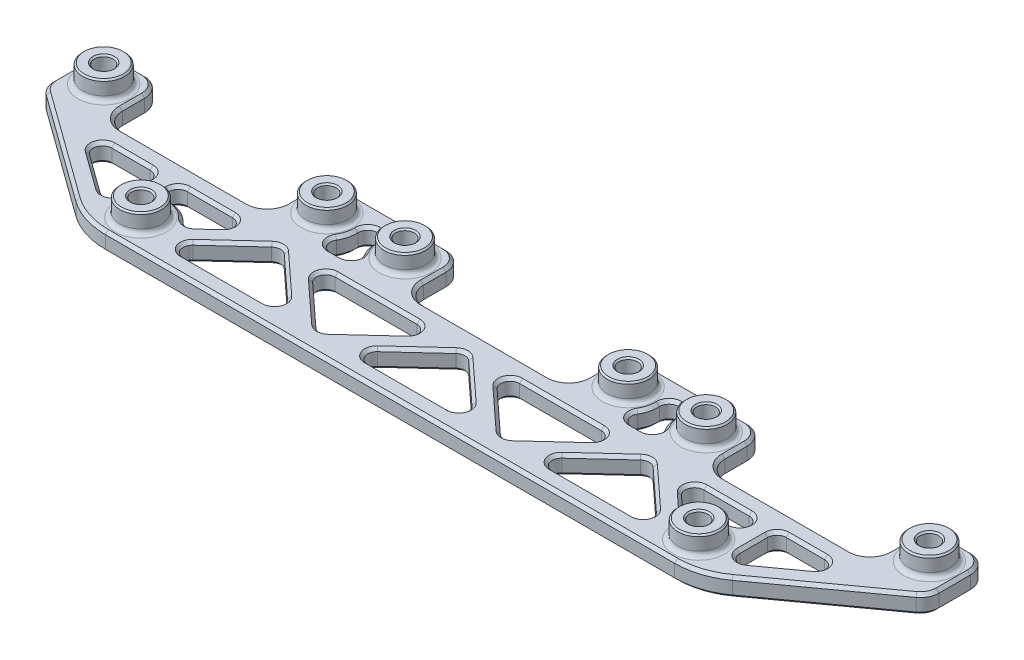
SolidWorks part; units mm, degrees
ref_plane "Front" through (0, 0, 0) normal (0, 0, 1) x (1, 0, 0)
ref_plane "Top" through (0, 0, 0) normal (0, 1, 0) x (1, 0, 0)
ref_plane "Right" through (0, 0, 0) normal (1, 0, 0) x (0, 0, -1)
sketch "Sketch2" plane through (0, 0, 0) normal (0, 1, 0) x (1, 0, 0)
  line L0 (-69.215, 13.335) -> (-68.58, 13.335) construction
  line L5 (-75.565, 3.175) -> (-65.405, 3.175) construction
  line L6 (-75.565, 3.175) -> (-75.565, 13.335) construction
  line L7 (-75.565, 13.335) -> (-65.405, 13.335) construction
  line L8 (-65.405, 3.175) -> (-65.405, 13.335) construction
  line L9 (-75.565, 3.175) -> (-65.405, 13.335) construction
  line L10 (-75.565, 13.335) -> (-65.405, 3.175) construction
  line L11 (-65.405, 10.16) -> (-65.405, 9.525) construction
  line L12 (-34.29, 13.335) -> (-33.655, 13.335) construction
  line L13 (-27.305, 3.175) -> (-37.465, 3.175) construction
  line L14 (-27.305, 3.175) -> (-27.305, 13.335) construction
  line L15 (-27.305, 13.335) -> (-37.465, 13.335) construction
  line L16 (-37.465, 3.175) -> (-37.465, 13.335) construction
  line L17 (-27.305, 3.175) -> (-37.465, 13.335) construction
  line L18 (-27.305, 13.335) -> (-37.465, 3.175) construction
  line L19 (-37.465, 9.525) -> (-37.465, 10.16) construction
  line L20 (-17.78, 13.335) -> (-17.145, 13.335) construction
  line L21 (-24.13, 3.175) -> (-13.97, 3.175) construction
  line L22 (-24.13, 3.175) -> (-24.13, 13.335) construction
  line L23 (-24.13, 13.335) -> (-13.97, 13.335) construction
  line L24 (-13.97, 3.175) -> (-13.97, 13.335) construction
  line L25 (-24.13, 3.175) -> (-13.97, 13.335) construction
  line L26 (-24.13, 13.335) -> (-13.97, 3.175) construction
  line L27 (-13.97, 10.16) -> (-13.97, 9.525) construction
  line L28 (17.145, 13.335) -> (17.78, 13.335) construction
  line L29 (24.13, 3.175) -> (13.97, 3.175) construction
  line L30 (24.13, 3.175) -> (24.13, 13.335) construction
  line L31 (24.13, 13.335) -> (13.97, 13.335) construction
  line L32 (13.97, 3.175) -> (13.97, 13.335) construction
  line L33 (24.13, 3.175) -> (13.97, 13.335) construction
  line L34 (24.13, 13.335) -> (13.97, 3.175) construction
  line L35 (13.97, 9.525) -> (13.97, 10.16) construction
  line L36 (37.465, 10.16) -> (37.465, 9.525) construction
  line L37 (27.305, 3.175) -> (37.465, 3.175) construction
  line L38 (27.305, 3.175) -> (27.305, 13.335) construction
  line L39 (27.305, 13.335) -> (37.465, 13.335) construction
  line L40 (37.465, 3.175) -> (37.465, 13.335) construction
  line L41 (27.305, 3.175) -> (37.465, 13.335) construction
  line L42 (27.305, 13.335) -> (37.465, 3.175) construction
  line L43 (33.655, 13.335) -> (34.29, 13.335) construction
  line L44 (68.58, 13.335) -> (69.215, 13.335) construction
  line L45 (75.565, 3.175) -> (65.405, 3.175) construction
  line L46 (75.565, 3.175) -> (75.565, 13.335) construction
  line L47 (75.565, 13.335) -> (65.405, 13.335) construction
  line L48 (65.405, 3.175) -> (65.405, 13.335) construction
  line L49 (75.565, 3.175) -> (65.405, 13.335) construction
  line L50 (75.565, 13.335) -> (65.405, 3.175) construction
  line L51 (65.405, 9.525) -> (65.405, 10.16) construction
  line L53 (-52.7114, -13.3477) -> (-42.5386, -13.3477) construction
  line L54 (-52.7114, -13.3477) -> (-52.7114, -3.175) construction
  line L55 (-52.7114, -3.175) -> (-42.5386, -3.175) construction
  line L57 (-52.7114, -13.3477) -> (-42.5386, -3.175) construction
  line L58 (-52.7114, -3.175) -> (-42.5386, -13.3477) construction
  line L59 (-45.7136, -13.3477) -> (-47.1551, -13.3477) construction
  line L60 (47.1551, -13.3477) -> (45.7136, -13.3477) construction
  line L61 (42.5386, -13.3477) -> (52.7113, -13.3477) construction
  line L63 (42.5387, -3.175) -> (52.7113, -3.175) construction
  line L64 (52.7113, -13.3477) -> (52.7113, -3.175) construction
  line L65 (42.5386, -13.3477) -> (52.7113, -3.175) construction
  line L66 (42.5387, -3.175) -> (52.7113, -13.3477) construction
  line L67 (-42.5386, -13.3477) -> (-42.5386, -3.175) construction
  line L70 (-42.5386, -13.3477) -> (-52.7114, -13.3477)
  line L71 (-52.7114, -13.3477) -> (-75.565, 3.175)
  line L72 (-75.565, 3.175) -> (-75.565, 13.335)
  line L73 (-75.565, 13.335) -> (-65.405, 13.335)
  line L74 (-65.405, 13.335) -> (-65.405, 3.175)
  line L75 (-65.405, 3.175) -> (-37.465, 3.175)
  line L76 (-37.465, 3.175) -> (-37.465, 13.335)
  line L77 (-37.465, 13.335) -> (-13.97, 13.335)
  line L78 (-13.97, 13.335) -> (-13.97, 3.175)
  line L79 (-13.97, 3.175) -> (13.97, 3.175)
  line L80 (13.97, 3.175) -> (13.97, 13.335)
  line L81 (13.97, 13.335) -> (37.465, 13.335)
  line L82 (37.465, 13.335) -> (37.465, 3.175)
  line L83 (37.465, 3.175) -> (65.405, 3.175)
  line L84 (65.405, 3.175) -> (65.405, 13.335)
  line L85 (65.405, 13.335) -> (75.565, 13.335)
  line L86 (75.565, 13.335) -> (75.565, 3.175)
  line L87 (75.565, 3.175) -> (52.7113, -13.3477)
  line L88 (52.7113, -13.3477) -> (42.5386, -13.3477)
  line L91 (-65.7544, 0) -> (-52.7114, 0)
  line L92 (75.565, 0) -> (-75.565, 0) construction
  line L93 (-52.7114, 0) -> (-52.7114, -9.4298)
  line L94 (-52.7114, -9.4298) -> (-65.7544, 0)
  line L95 (-59.2329, -4.7149) -> (-61.0931, -7.2879) construction
  line L96 (65.7544, 0) -> (52.7113, 0)
  line L97 (52.7113, 0) -> (52.7113, -9.4298)
  line L98 (52.7113, -9.4298) -> (65.7544, 0)
  line L99 (59.2329, -4.7149) -> (61.0931, -7.2879) construction
  line L105 (-42.5386, -3.175) -> (-42.5386, 0) construction
  line L106 (42.5387, -3.175) -> (42.5386, -13.3477) construction
  line L107 (42.5386, -13.3477) -> (-42.5386, -13.3477)
  line L108 (-42.5386, -8.7313) -> (-42.5386, -10.1727) construction
  line L109 (42.5386, -10.1727) -> (42.5386, -8.7313) construction
  line L110 (-42.5386, -10.1727) -> (42.5386, -10.1727) construction
  line L111 (0, -10.1727) -> (0, -13.3477) construction
  line L112 (0, 0) -> (-11.0538, -10.1727)
  line L113 (-11.0538, -10.1727) -> (11.0538, -10.1727)
  line L114 (11.0538, -10.1727) -> (0, 0)
  line L115 (-4.6886, 0) -> (-15.7424, -10.1727)
  line L116 (-15.7424, -10.1727) -> (-26.7962, 0)
  line L117 (-26.7962, 0) -> (-4.6886, 0)
  line L118 (-42.5386, -10.1727) -> (-20.431, -10.1727)
  line L119 (4.6886, 0) -> (15.7424, -10.1727)
  line L120 (15.7424, -10.1727) -> (26.7962, 0)
  line L121 (26.7962, 0) -> (4.6886, 0)
  line L122 (-42.5386, 0) -> (42.5387, 0) construction
  line L123 (42.5387, 0) -> (42.5387, -3.175) construction
  line L127 (7.6769, -2.7501) -> (5.5269, -5.0864) construction
  line L128 (42.5386, -10.1727) -> (31.4848, 0)
  line L129 (-5.5269, -5.0864) -> (-7.6769, -2.7501) construction
  line L130 (-28.9462, -2.3362) -> (-26.7962, 0) construction
  line L131 (-42.5386, 0) -> (-42.5386, -5.8578) construction
  line L132 (-42.5386, -5.8578) -> (-36.1735, 0)
  line L133 (-36.1735, 0) -> (-42.5386, 0)
  line L134 (-39.3561, -2.9289) -> (-37.206, -5.2652) construction
  line L135 (42.5387, 0) -> (42.5386, -5.8578) construction
  line L136 (42.5386, -5.8578) -> (36.1735, 0)
  line L137 (36.1735, 0) -> (42.5387, 0)
  line L138 (39.3561, -2.9289) -> (37.206, -5.2652) construction
  line L139 (31.4848, 0) -> (20.431, -10.1727)
  line L140 (20.431, -10.1727) -> (42.5386, -10.1727)
  line L141 (-42.5386, -10.1727) -> (-31.4848, 0)
  line L142 (-31.4848, 0) -> (-20.431, -10.1727)
  line L143 (18.281, -7.8365) -> (20.431, -10.1727) construction
  line L144 (-27.6757, 10.16) -> (-23.7593, 10.16)
  line L145 (23.7593, 10.16) -> (27.6757, 10.16)
  line L146 (19.05, 3.175) -> (32.385, 3.175)
  line L148 (49.5363, 0) -> (49.5363, -3.5478)
  line L149 (-32.385, 3.175) -> (-19.05, 3.175)
  line L151 (42.5387, 0) -> (49.5363, 0)
  line L152 (49.5363, 0) -> (52.7113, 0) construction
  line L154 (-49.5364, 0) -> (-49.5364, -3.5478)
  line L156 (-52.7114, 0) -> (-49.5364, 0) construction
  line L157 (-49.5364, 0) -> (-42.5386, 0)
  line L158 (-42.5386, -5.8578) -> (-42.9565, -6.2424)
  line L159 (42.5386, -5.8578) -> (42.9565, -6.2424)
  circle A0 centre (-32.385, 8.255) radius 5.08 construction
  circle A1 centre (-19.05, 8.255) radius 5.08 construction
  circle A2 centre (19.05, 8.255) radius 5.08 construction
  circle A3 centre (32.385, 8.255) radius 5.08 construction
  arc A4 (-27.6757, 10.16) -> (-32.385, 3.175) centre (-32.385, 8.255) cw
  arc A5 (-23.7593, 10.16) -> (-19.05, 3.175) centre (-19.05, 8.255) ccw
  arc A6 (27.6757, 10.16) -> (32.385, 3.175) centre (32.385, 8.255) ccw
  arc A7 (23.7593, 10.16) -> (19.05, 3.175) centre (19.05, 8.255) cw
  circle A8 centre (-47.625, -8.2614) radius 5.0864 construction
  circle A9 centre (47.625, -8.2614) radius 5.0864 construction
  arc A12 (-49.5364, -3.5478) -> (-42.9565, -6.2424) centre (-47.625, -8.2614) cw
  arc A13 (42.9565, -6.2424) -> (49.5363, -3.5478) centre (47.625, -8.2614) cw
  point P0 (-70.485, 8.255)
  point P11 (-32.385, 8.255)
  point P21 (-19.05, 8.255)
  point P31 (19.05, 8.255)
  point P41 (32.385, 8.255)
  point P51 (70.485, 8.255)
  point P61 (-47.625, -8.2614)
  point P71 (47.625, -8.2614)
  dimension "D1" = 3.175
  dimension "D2" = 3.175
extrude "Boss-Extrude2" add sketch "Sketch2" along normal blind 3.175
sketch "Sketch3" plane through (0, 3.175, 0) normal (0, 1, 0) x (1, 0, 0)
  line L0 (75.565, 13.335) -> (65.405, 13.335) construction
  line L1 (75.565, 3.175) -> (75.565, 13.335) construction
  line L2 (65.405, 13.335) -> (65.405, 3.175) construction
  line L3 (-65.405, 13.335) -> (-75.565, 13.335) construction
  line L4 (-65.405, 3.175) -> (-65.405, 13.335) construction
  line L5 (-75.565, 13.335) -> (-75.565, 3.175) construction
  circle A0 centre (-70.485, 8.255) radius 5.08 construction
  circle A1 centre (-32.385, 8.255) radius 3.5719
  circle A2 centre (-19.05, 8.255) radius 3.5719
  circle A3 centre (19.05, 8.255) radius 3.5719
  circle A4 centre (32.385, 8.255) radius 3.5719
  circle A5 centre (70.485, 8.255) radius 5.08 construction
  arc A6 (-32.385, 3.175) -> (-27.6757, 10.16) centre (-32.385, 8.255) ccw construction
  arc A7 (-23.7593, 10.16) -> (-19.05, 3.175) centre (-19.05, 8.255) ccw construction
  arc A8 (19.05, 3.175) -> (23.7593, 10.16) centre (19.05, 8.255) ccw construction
  arc A9 (27.6757, 10.16) -> (32.385, 3.175) centre (32.385, 8.255) ccw construction
  circle A10 centre (70.485, 8.255) radius 3.5719
  circle A11 centre (-70.485, 8.255) radius 3.5719
  circle A14 centre (-47.625, -8.2614) radius 3.5719
  circle A15 centre (47.625, -8.2614) radius 3.5719
  arc A17 (-42.9565, -6.2424) -> (-49.5364, -3.5478) centre (-47.625, -8.2614) ccw construction
  arc A18 (49.5363, -3.5478) -> (42.9565, -6.2424) centre (47.625, -8.2614) ccw construction
  dimension "D1" = 7.1437
extrude "Boss-Extrude3" add sketch "Sketch3" along normal blind 3.175
sketch "Sketch4" plane through (0, 0, 0) normal (0, -1, 0) x (1, 0, 0)
  circle A0 centre (-70.485, -8.255) radius 1.5875
  circle A1 centre (-32.385, -8.255) radius 1.5875
  circle A2 centre (-19.05, -8.255) radius 1.5875
  circle A3 centre (19.05, -8.255) radius 1.5875
  circle A4 centre (32.385, -8.255) radius 1.5875
  circle A5 centre (70.485, -8.255) radius 1.5875
  circle A6 centre (70.485, -8.255) radius 3.5719 construction
  circle A7 centre (32.385, -8.255) radius 3.5719 construction
  circle A8 centre (19.05, -8.255) radius 3.5719 construction
  circle A9 centre (-19.05, -8.255) radius 3.5719 construction
  circle A10 centre (-32.385, -8.255) radius 3.5719 construction
  circle A11 centre (-70.485, -8.255) radius 3.5719 construction
  circle A12 centre (47.625, 8.2614) radius 1.5875
  circle A13 centre (-47.625, 8.2614) radius 1.5875
  dimension "D1" = 3.175
extrude "Cut-Extrude1" cut sketch "Sketch4" against normal up to next
fillet "Fillet2" radius 12.7 2 edges at (-52.7114, 1.5875, 13.3477) (52.7113, 1.5875, 13.3477)
fillet "Fillet1" radius 3.175 16 edges at (-65.405, 1.5875, -3.175) (-37.465, 1.5875, -3.175) (-37.465, 1.5875, -13.335) (-13.97, 1.5875, -13.335) (-13.97, 1.5875, -3.175) (13.97, 1.5875, -3.175) (13.97, 1.5875, -13.335) (37.465, 1.5875, -13.335) (37.465, 1.5875, -3.175) (65.405, 1.5875, -3.175) (65.405, 1.5875, -13.335) (75.565, 1.5875, -3.175) (-75.565, 1.5875, -3.175) (-75.565, 1.5875, -13.335) (-65.405, 1.5875, -13.335) (75.565, 1.5875, -13.335)
fillet "Fillet3" radius 1.5875 37 edges at (23.7593, 1.5875, -10.16) (19.05, 1.5875, -3.175) (32.385, 1.5875, -3.175) (27.6757, 1.5875, -10.16) (-19.05, 1.5875, -3.175) (-23.7593, 1.5875, -10.16) (-27.6757, 1.5875, -10.16) (-32.385, 1.5875, -3.175) (36.1735, 1.5875, 0) (26.7962, 1.5875, 0) (4.6886, 1.5875, 0) (-42.5386, 1.5875, 10.1727) (-20.431, 1.5875, 10.1727) (-31.4848, 1.5875, 0) (-15.7424, 1.5875, 10.1727) (-4.6886, 1.5875, 0) (-26.7962, 1.5875, 0) (-11.0538, 1.5875, 10.1727) (11.0538, 1.5875, 10.1727) (0, 1.5875, 0) (31.4848, 1.5875, 0) (20.431, 1.5875, 10.1727) (42.5386, 1.5875, 10.1727) (-36.1735, 1.5875, 0) (-52.7114, 1.5875, 0) (-65.7544, 1.5875, 0) (-52.7114, 1.5875, 9.4298) (15.7424, 1.5875, 10.1727) (52.7113, 1.5875, 0) (65.7544, 1.5875, 0) (52.7113, 1.5875, 9.4298) (-49.5364, 1.5875, 3.5478) (-42.9565, 1.5875, 6.2424) (-49.5364, 1.5875, 0) (42.9565, 1.5875, 6.2424) (49.5363, 1.5875, 3.5478) (49.5363, 1.5875, 0)
fillet "Fillet4" radius 0.7937 8 edges at (70.485, 3.175, -4.6831) (47.625, 3.175, 11.8332) (32.385, 3.175, -4.6831) (19.05, 3.175, -4.6831) (-19.05, 3.175, -4.6831) (-32.385, 3.175, -4.6831) (-47.625, 3.175, 11.8332) (-70.485, 3.175, -4.6831)
chamfer "Chamfer1" distance 0.508 angle 45 220 edges at (24.561, 3.175, -9.668) (23.9698, 3.175, -6.9891) (23.3439, 3.175, -3.9879) (25.7175, 3.175, -3.175) (28.0911, 3.175, -3.9879) (27.4652, 3.175, -6.9891) (26.874, 3.175, -9.668) (25.7175, 3.175, -10.16) (-23.3439, 3.175, -3.9879) (-23.9698, 3.175, -6.9891) (-24.561, 3.175, -9.668) (-25.7175, 3.175, -10.16) (-26.874, 3.175, -9.668) (-27.4652, 3.175, -6.9891) (-28.0911, 3.175, -3.9879) (-25.7175, 3.175, -3.175) (42.7312, 3.175, 5.393) (45.6641, 3.175, 3.5682) (49.0438, 3.175, 2.7448) (49.5363, 3.175, 1.5914) (49.0714, 3.175, 0.465) (44.0958, 3.175, 0) (38.7638, 3.175, 1.0105) (40.3738, 3.175, 3.8655) (15.7424, 3.175, 9.6028) (20.3097, 3.175, 5.9695) (24.2059, 3.175, 1.0105) (15.7424, 3.175, 0) (7.279, 3.175, 1.0105) (11.1752, 3.175, 5.9695) (-39.9483, 3.175, 9.1622) (-31.4848, 3.175, 10.1727) (-23.0214, 3.175, 9.1622) (-26.9176, 3.175, 4.2032) (-31.4848, 3.175, 0.5699) (-36.0521, 3.175, 4.2032) (-15.7424, 3.175, 9.6028) (-11.1752, 3.175, 5.9695) (-7.279, 3.175, 1.0105) (-15.7424, 3.175, 0) (-24.2059, 3.175, 1.0105) (-20.3097, 3.175, 5.9695) (-8.4634, 3.175, 9.1622) (0, 3.175, 10.1727) (8.4634, 3.175, 9.1622) (4.5673, 3.175, 4.2032) (0, 3.175, 0.5699) (-4.5673, 3.175, 4.2032) (31.4848, 3.175, 0.5699) (26.9176, 3.175, 4.2032) (23.0214, 3.175, 9.1622) (31.4848, 3.175, 10.1727) (39.9483, 3.175, 9.1622) (36.0521, 3.175, 4.2032) (-49.0438, 3.175, 2.7448) (-45.6641, 3.175, 3.5682) (-42.7312, 3.175, 5.393) (-40.3738, 3.175, 3.8655) (-38.7638, 3.175, 1.0105) (-44.0958, 3.175, 0) (-49.0714, 3.175, 0.465) (-49.5364, 3.175, 1.5914) (53.1763, 3.175, 0.465) (52.7113, 3.175, 3.9553) (53.5765, 3.175, 7.7368) (58.5041, 3.175, 5.2418) (62.3594, 3.175, 1.0987) (57.574, 3.175, 0) (-53.1763, 3.175, 0.465) (-57.574, 3.175, 0) (-62.3594, 3.175, 1.0987) (-58.5041, 3.175, 5.2418) (-53.5765, 3.175, 7.7368) (-52.7114, 3.175, 3.9553) (-14.8999, 3.175, -12.4051) (-13.97, 3.175, -8.255) (-13.0401, 3.175, -4.1049) (0, 3.175, -3.175) (13.0401, 3.175, -4.1049) (13.97, 3.175, -8.255) (14.8999, 3.175, -12.4051) (25.7175, 3.175, -13.335) (36.5351, 3.175, -12.4051) (37.465, 3.175, -8.255) (38.3949, 3.175, -4.1049) (51.435, 3.175, -3.175) (64.4751, 3.175, -4.1049) (65.405, 3.175, -8.255) (66.3349, 3.175, -12.4051) (70.485, 3.175, -13.335) (74.6351, 3.175, -12.4051) (75.565, 3.175, -7.4787) (75.2173, 3.175, -3.3527) (65.1462, 3.175, 4.3576) (52.5117, 3.175, 12.7307) (0, 3.175, 13.3477) (-52.5117, 3.175, 12.7307) (-65.1462, 3.175, 4.3576) (-75.2173, 3.175, -3.3527) (-75.565, 3.175, -7.4787) (-74.6351, 3.175, -12.4051) (-70.485, 3.175, -13.335) (-66.3349, 3.175, -12.4051) (-65.405, 3.175, -8.255) (-64.4751, 3.175, -4.1049) (-51.435, 3.175, -3.175) (-38.3949, 3.175, -4.1049) (-37.465, 3.175, -8.255) (-36.5351, 3.175, -12.4051) (-25.7175, 3.175, -13.335) (23.9698, 0, -6.9891) (23.3439, 0, -3.9879) (24.561, 0, -9.668) (25.7175, 0, -3.175) (25.7175, 0, -10.16) (28.0911, 0, -3.9879) (26.874, 0, -9.668) (27.4652, 0, -6.9891) (-27.4652, 0, -6.9891) (-28.0911, 0, -3.9879) (-26.874, 0, -9.668) (-25.7175, 0, -3.175) (-25.7175, 0, -10.16) (-23.3439, 0, -3.9879) (-24.561, 0, -9.668) (-23.9698, 0, -6.9891) (-53.5765, 0, 7.7368) (-52.7114, 0, 3.9553) (-58.5041, 0, 5.2418) (-53.1763, 0, 0.465) (-62.3594, 0, 1.0987) (-57.574, 0, 0) (-49.5364, 0, 1.5914) (-49.0438, 0, 2.7448) (-49.0714, 0, 0.465) (-45.6641, 0, 3.5682) (-44.0958, 0, 0) (-42.7312, 0, 5.393) (-38.7638, 0, 1.0105) (-40.3738, 0, 3.8655) (-39.9483, 0, 9.1622) (-31.4848, 0, 10.1727) (-36.0521, 0, 4.2032) (-23.0214, 0, 9.1622) (-31.4848, 0, 0.5699) (-26.9176, 0, 4.2032) (-24.2059, 0, 1.0105) (-20.3097, 0, 5.9695) (-15.7424, 0, 0) (-15.7424, 0, 9.6028) (-7.279, 0, 1.0105) (-11.1752, 0, 5.9695) (-8.4634, 0, 9.1622) (0, 0, 10.1727) (-4.5673, 0, 4.2032) (8.4634, 0, 9.1622) (0, 0, 0.5699) (4.5673, 0, 4.2032) (7.279, 0, 1.0105) (11.1752, 0, 5.9695) (15.7424, 0, 0) (15.7424, 0, 9.6028) (24.2059, 0, 1.0105) (20.3097, 0, 5.9695) (39.9483, 0, 9.1622) (36.0521, 0, 4.2032) (31.4848, 0, 10.1727) (31.4848, 0, 0.5699) (23.0214, 0, 9.1622) (26.9176, 0, 4.2032) (45.6641, 0, 3.5682) (49.0438, 0, 2.7448) (42.7312, 0, 5.393) (49.5363, 0, 1.5914) (40.3738, 0, 3.8655) (49.0714, 0, 0.465) (38.7638, 0, 1.0105) (44.0958, 0, 0) (53.5765, 0, 7.7368) (58.5041, 0, 5.2418) (52.7113, 0, 3.9553) (62.3594, 0, 1.0987) (53.1763, 0, 0.465) (57.574, 0, 0) (0, 0, 13.3477) (52.5117, 0, 12.7307) (-52.5117, 0, 12.7307) (65.1462, 0, 4.3576) (-65.1462, 0, 4.3576) (75.2173, 0, -3.3527) (-75.2173, 0, -3.3527) (75.565, 0, -7.4787) (-75.565, 0, -7.4787) (74.6351, 0, -12.4051) (-74.6351, 0, -12.4051) (70.485, 0, -13.335) (-70.485, 0, -13.335) (66.3349, 0, -12.4051) (-66.3349, 0, -12.4051) (65.405, 0, -8.255) (-65.405, 0, -8.255) (64.4751, 0, -4.1049) (-64.4751, 0, -4.1049) (51.435, 0, -3.175) (-51.435, 0, -3.175) (38.3949, 0, -4.1049) (-38.3949, 0, -4.1049) (37.465, 0, -8.255) (-37.465, 0, -8.255) (36.5351, 0, -12.4051) (-36.5351, 0, -12.4051) (25.7175, 0, -13.335) (-25.7175, 0, -13.335) (14.8999, 0, -12.4051) (-14.8999, 0, -12.4051) (13.97, 0, -8.255) (-13.97, 0, -8.255) (13.0401, 0, -4.1049) (-13.0401, 0, -4.1049) (0, 0, -3.175)
chamfer "Chamfer2" distance 0.254 angle 45 24 edges at (70.485, 0, -9.8425) (70.485, 6.35, -6.6675) (47.625, 0, 6.6739) (47.625, 6.35, 9.8489) (32.385, 0, -9.8425) (32.385, 6.35, -6.6675) (19.05, 0, -9.8425) (19.05, 6.35, -6.6675) (-19.05, 0, -9.8425) (-19.05, 6.35, -6.6675) (-32.385, 0, -9.8425) (-32.385, 6.35, -6.6675) (-47.625, 0, 6.6739) (-47.625, 6.35, 9.8489) (-70.485, 0, -9.8425) (-70.485, 6.35, -6.6675) (70.485, 6.35, -4.6831) (47.625, 6.35, 11.8332) (32.385, 6.35, -4.6831) (19.05, 6.35, -4.6831) (-19.05, 6.35, -4.6831) (-32.385, 6.35, -4.6831) (-47.625, 6.35, 11.8332) (-70.485, 6.35, -4.6831)
equation "\"D2@Sketch2\"=\"D1@Sketch2\""
